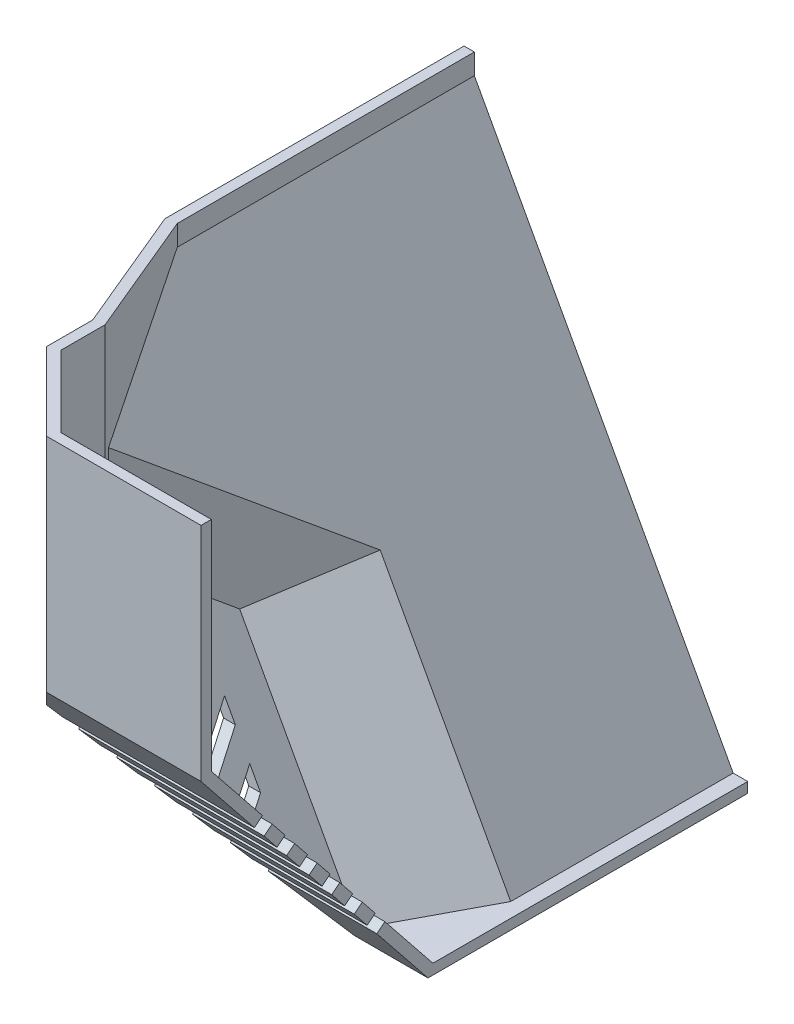
SolidWorks part; units mm, degrees
ref_plane "Plan de face" through (0, 0, 0) normal (0, 0, 1) x (1, 0, 0)
ref_plane "Plan de dessus" through (0, 0, 0) normal (0, 1, 0) x (1, 0, 0)
ref_plane "Plan de droite" through (0, 0, 0) normal (1, 0, 0) x (0, 0, -1)
sketch "Esquisse1" plane through (0, 0, 0) normal (0, 0, 1) x (1, 0, 0)
  line L1 (0, 0) -> (275, 0)
  line L2 (0, 0) -> (0, 490)
  line L3 (0, 490) -> (275, 490)
  line L4 (275, 0) -> (275, 490)
  dimension "D1" = 275
  dimension "D2" = 490
extrude "Boss.-Extru.1" add sketch "Esquisse1" along normal blind 550
sketch "Esquisse2" plane through (0, 490, 0) normal (0, 1, 0) x (1, 0, 0)
  line L0 (275, -530) -> (125, -530)
  line L1 (275, -550) -> (275, 0) construction
  line L2 (125, -530) -> (50, -455)
  line L3 (0, -550) -> (0, 0) construction
  line L4 (0, -290) -> (0, -530) construction
  line L5 (0, -530) -> (125, -530) construction
  line L6 (275, -530) -> (275, -619.0675)
  line L7 (275, -619.0675) -> (-74.3807, -619.0675)
  line L8 (-74.3807, -619.0675) -> (-74.3807, -290)
  line L9 (-74.3807, -290) -> (0, -290)
  line L10 (275, -550) -> (0, -550) construction
  line L11 (50, -455) -> (50, -410)
  line L12 (50, -410) -> (0, -290)
  line L13 (125, -530) -> (125, -455) construction
  line L14 (125, -455) -> (50, -455) construction
  line L15 (50, -410) -> (0, -410) construction
  dimension "D1" = 20
  dimension "D2" = 150
  dimension "D3" = 45
  dimension "D4" = 120
  dimension "D5" = 120
  dimension "D6" = 50
extrude "Enlèv. mat.-Extru.1" cut sketch "Esquisse2" against normal through all
sketch "Esquisse3" plane through (275, 0, 0) normal (1, 0, 0) x (0, 0, -1)
  line L0 (-310, 0) -> (-530, 275)
  line L1 (-530, 0) -> (0, 0) construction
  line L2 (-530, 0) -> (-530, 490) construction
  line L3 (-530, 275) -> (-530, 0)
  line L4 (-530, 0) -> (-310, 0)
  line L5 (-530, 0) -> (-510, 0) construction
  line L6 (-510, 0) -> (-510, 250) construction
  line L7 (-510, 250) -> (-530, 275) construction
  dimension "D1" = 200
  dimension "D2" = 250
  dimension "D3" = 220
extrude "Enlèv. mat.-Extru.2" cut sketch "Esquisse3" against normal through all
sketch "Esquisse4" plane through (0, 0, 0) normal (0, 0, -1) x (-1, 0, 0)
  line L0 (-255, 0) -> (0, 0)
  line L1 (0, 0) -> (-275, 0) construction
  line L2 (0, 0) -> (45, 0) construction
  line L3 (45, 0) -> (45, 550) construction
  line L4 (45, 550) -> (0, 467.5) construction
  line L5 (0, 490) -> (0, 0) construction
  line L6 (0, 467.5) -> (-255, 0)
  line L7 (0, 467.5) -> (0, 0)
  dimension "D1" = 300
  dimension "D2" = 550
  dimension "D3" = 255
extrude "Enlèv. mat.-Extru.3" cut sketch "Esquisse4" against normal blind 310
chamfer "Chanfrein1" distance 100 angle 45 1 edges at (8.3333, 226.1111, 310) first distance on face at (19.4444, 337.4537, 336.6667)
chamfer "Chanfrein2" distance 45 angle 65 1 edges at (169.902, 156.0131, 310) first distance on face at (141.5359, 104.0087, 310)
sketch "Esquisse6" plane through (0, 0, 310) normal (0, 0, -1) x (-1, 0, 0)
  line L0 (-84.8039, 0) -> (-203.7411, 0)
  line L1 (-203.7411, 0) -> (-84.8039, 218.0514)
  line L2 (-84.8039, 218.0514) -> (-4.9032, 364.5361)
  line L3 (-4.9032, 364.5361) -> (-4.9032, 0)
  line L4 (-4.9032, 0) -> (-84.8039, 0)
extrude "Enlèv. mat.-Extru.5" cut sketch "Esquisse6" against normal blind 550
shell "Coque1" thickness 10
sketch "Esquisse7" plane through (275, 0, 0) normal (1, 0, 0) x (0, 0, -1)
  line L0 (-478.2594, 210.3242) -> (-431.8905, 247.4194) construction
  line L1 (-310, 0) -> (-530, 275) construction
  line L2 (-431.8905, 247.4194) -> (-350, 185.6001) construction
  line L3 (-350, 185.6001) -> (-350, 50) construction
  line L4 (-350, 50) -> (-478.2594, 210.3242) construction
  line L5 (-310, 218.0514) -> (-310, 0) construction
  line L6 (-431.8905, 247.4194) -> (-478.2594, 210.3242)
  line L7 (-478.2594, 210.3242) -> (-468.889, 198.6112)
  line L8 (-402.3077, 287.7347) -> (-310, 218.0514) construction
  line L9 (-487.6298, 222.0373) -> (-310, 0) construction
  line L10 (-468.889, 198.6112) -> (-419.5364, 238.0933)
  line L11 (-431.8905, 247.4194) -> (-419.5364, 238.0933)
  line L12 (-456.3951, 182.9938) -> (-355.4275, 263.7679) construction
  line L13 (-447.0246, 171.2808) -> (-346.0571, 252.0548) construction
  line L14 (-355.4275, 263.7679) -> (-346.0571, 252.0548) construction
  line L15 (-425.1603, 143.9504) -> (-324.1928, 224.7244) construction
  line L16 (-434.5307, 155.6634) -> (-333.5632, 236.4374) construction
  line L17 (-403.296, 116.62) -> (-302.3285, 197.394) construction
  line L18 (-412.6664, 128.333) -> (-311.6989, 209.107) construction
  line L19 (-381.4317, 89.2896) -> (-280.4641, 170.0636) construction
  line L20 (-390.8021, 101.0026) -> (-289.8346, 181.7766) construction
  line L21 (-359.5673, 61.9592) -> (-258.5998, 142.7332) construction
  line L22 (-368.9378, 73.6722) -> (-267.9702, 154.4462) construction
  line L23 (-456.3951, 182.9938) -> (-447.0246, 171.2808)
  line L24 (-447.0246, 171.2808) -> (-390.7102, 216.3323)
  line L25 (-390.7102, 216.3323) -> (-403.0643, 225.6585)
  line L26 (-403.0643, 225.6585) -> (-456.3951, 182.9938)
  line L27 (-434.5307, 155.6634) -> (-425.1603, 143.9504)
  line L28 (-425.1603, 143.9504) -> (-361.884, 194.5714)
  line L29 (-361.884, 194.5714) -> (-374.2381, 203.8975)
  line L30 (-374.2381, 203.8975) -> (-434.5307, 155.6634)
  line L31 (-434.5307, 155.6634) -> (-412.6664, 128.333)
  line L32 (-412.6664, 128.333) -> (-403.296, 116.62)
  line L33 (-403.296, 116.62) -> (-350, 159.2568)
  line L34 (-350, 159.2568) -> (-350, 178.4661)
  line L35 (-350, 178.4661) -> (-412.6664, 128.333)
  line L36 (-390.8021, 101.0026) -> (-381.4317, 89.2896)
  line L37 (-381.4317, 89.2896) -> (-350, 114.4349)
  line L38 (-350, 114.4349) -> (-350, 133.6443)
  line L39 (-350, 133.6443) -> (-390.8021, 101.0026)
  line L40 (-368.9378, 73.6722) -> (-359.5673, 61.9592)
  line L41 (-359.5673, 61.9592) -> (-350, 69.613)
  line L42 (-350, 69.613) -> (-350, 88.8224)
  line L43 (-350, 88.8224) -> (-368.9378, 73.6722)
  line M12 (-530, 275) -> (-310, 0)
  dimension "D1" = 50
  dimension "D2" = 40
  dimension "D3" = 15
  dimension "D4" = 15
  dimension "D5" = 20
  dimension "D6" = 15
  dimension "D8" = 20
  dimension "D7" = 5
extrude "Enlèv. mat.-Extru.6" cut sketch "Esquisse7" against normal blind 550 contours L34 L35 L33 M12 | L38 L39 L37 M12 | L42 L43 L41 M12 | L29 L30 L28 M12 | L25 L26 L24 M12 | L11 L6 L10 M12 region at (275, 223.5574, 449.5874) region at (275, 74.3638, 357.383) region at (275, 109.9271, 368.1597) region at (275, 145.8772, 379.0537) region at (275, 174.4784, 398.9096) region at (275, 199.0186, 424.2493)
sketch "Esquisse8" plane through (275, 0, 0) normal (1, 0, 0) x (0, 0, -1)
  line L0 (-520, 480) -> (-520, 278.5078)
  line L1 (-520, 278.5078) -> (-305.1938, 10)
  line L2 (-305.1938, 10) -> (0, 10)
  line L3 (0, 0) -> (0, 490) construction
  line L4 (0, 10) -> (0, 490)
  line L5 (0, 490) -> (-520, 490)
  line L6 (-530, 490) -> (0, 490) construction
  line L7 (-520, 490) -> (-520, 480)
extrude "Enlèv. mat.-Extru.7" cut sketch "Esquisse8" against normal blind 10
sketch "Esquisse9" plane through (0, 0, 0) normal (0, 0, -1) x (-1, 0, 0)
  line L0 (-10, 470.0499) -> (-10, 490)
  line L1 (-265, 490) -> (0, 490) construction
  line L2 (-10, 490) -> (-275, 490)
  line L3 (-275, 490) -> (-275, 10)
  line L4 (-275, 10) -> (-260.9363, 10)
  line L5 (-260.9363, 10) -> (-10, 470.0499)
extrude "Enlèv. mat.-Extru.8" cut sketch "Esquisse9" against normal blind 10
sketch "Esquisse10" plane through (0, 490, 0) normal (0, 1, 0) x (1, 0, 0)
  line L0 (265, -10) -> (10, -10)
  line L1 (10, -10) -> (10, -288)
  line L2 (10, -288) -> (60, -408)
  line L3 (60, -408) -> (60, -450.8579)
  line L4 (60, -450.8579) -> (129.1421, -520)
  line L5 (129.1421, -520) -> (265, -520)
  line L6 (265, -520) -> (265, -10)
extrude "Enlèv. mat.-Extru.9" cut sketch "Esquisse10" against normal blind 10
